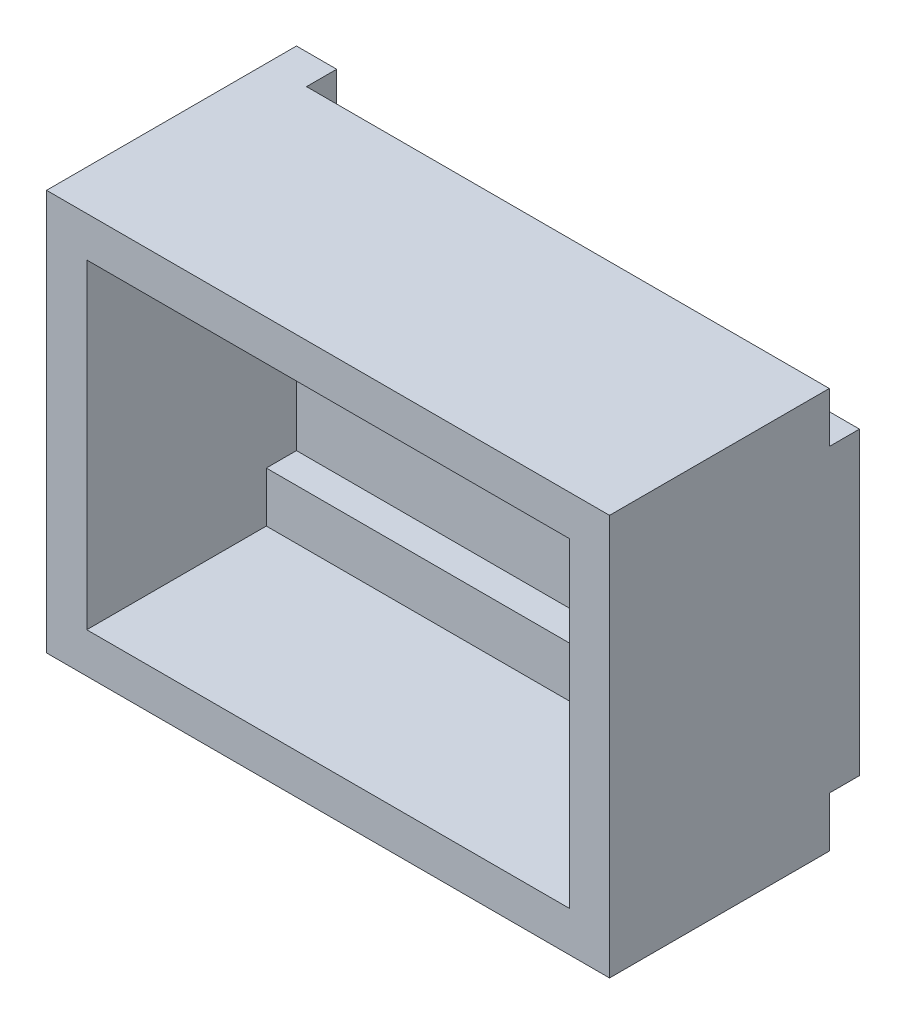
SolidWorks part; units mm, degrees
ref_plane "Front Plane" through (0, 0, 0) normal (1, 0, 0) x (0, 1, 0)
ref_plane "Top Plane" through (0, 0, 0) normal (0, 0, 1) x (0, 1, 0)
ref_plane "Right Plane" through (0, 0, 0) normal (0, 1, 0) x (-1, 0, 0)
sketch "Sketch2" plane through (0, 0, 0) normal (0, 0, 1) x (0, 1, 0)
  line L1 (-9.9636, -14) -> (9.9637, -14)
  line L2 (-9.9636, -14) -> (-9.9636, 14)
  line L3 (-9.9636, 14) -> (9.9637, 14)
  line L4 (9.9637, -14) -> (9.9637, 14)
  line L5 (-9.9636, -14) -> (9.9637, 14) construction
  line L6 (-9.9636, 14) -> (9.9637, -14) construction
  point P0 (0, 0)
  dimension "D1" = 28
  dimension "D2" = 19.9273
extrude "Boss-Extrude1" add sketch "Sketch2" along normal blind 12.4298
sketch "Sketch3" plane through (14, 0, 0) normal (1, 0, 0) x (0, 1, 0)
  line L0 (-9.9636, 12.4298) -> (9.9637, 12.4298) construction
  line L1 (-9.9636, 0) -> (-7.4636, 0)
  line L2 (-9.9636, 0) -> (-9.9636, 1.5)
  line L3 (-9.9636, 1.5) -> (-7.4636, 1.5)
  line L4 (-7.4636, 0) -> (-7.4636, 1.5)
  line L5 (9.9637, 0) -> (7.4637, 0)
  line L6 (9.9637, 0) -> (9.9637, 1.5)
  line L7 (9.9637, 1.5) -> (7.4637, 1.5)
  line L8 (7.4637, 0) -> (7.4637, 1.5)
  dimension "D1" = 10.9298
  dimension "D2" = 2.5
extrude "Cut-Extrude1" cut sketch "Sketch3" against normal offset from surface (26 mm away) 2 up to face at (-14, 0, 6.2149)
shell "Shell1" thickness 2 removed face at (0, 0, 12.4298)
equation "\"delta\"= 0.03mm"
equation "\"wall\"= 2mm"
equation "\"lip_t\"= 1.5mm"
equation "\"lip_w\"= 2mm"
equation "\"groove_extra\"= 0.5mm"
equation "\"end_gap\"= 0.5mm"
equation "\"W_hole_t\"= 20.0064mm"
equation "\"W_shaft_t\"= 19.9873mm"
equation "\"H_hole_t\"= 11.0051mm"
equation "\"H_shaft_t\"= 10.9898mm"
equation "\"lid_in_w\"= \"W_hole_t\" + 2 * \"delta\""
equation "\"box_w\"= \"W_shaft_t\" - 2 * \"delta\""
equation "\"lid_in_h\"= \"H_hole_t\" + 2 * \"delta\""
equation "\"box_rim_groove\"= \"H_shaft_t\" - 2 * \"delta\""
equation "\"box_h\"= \"box_rim_groove\" + \"lip_t\""
equation "\"cav_w\"= \"box_w\" - 2 * \"wall\""
equation "\"cav_h\" = \"box_h\" - 2 * \"wall\""
equation "\"cav_l\"= 24mm"
equation "\"box_l\"= \"cav_l\" + 2 * \"wall\""
equation "\"groove_w\"= \"lip_w\" + \"groove_extra\""
equation "\"groove_h\"= \"lip_t\""
equation "\"lid_w\"= \"lid_in_w\" + 2 * \"wall\""
equation "\"lid_h\"= \"lid_in_h\" + \"wall\" + \"lip_t\""
equation "\"lid_l\"= \"box_l\" + \"end_gap\" + \"wall\""
equation "\"D1@Sketch2\"=\"box_l\""
equation "\"D2@Sketch2\"=\"box_w\""
equation "\"D1@Boss-Extrude1\"=\"box_h\""
equation "\"D1@Sketch3\"=\"box_rim_groove\""
equation "\"D2@Sketch3\"=\"groove_w\""
equation "\"D1@Shell1\"=\"wall\""
